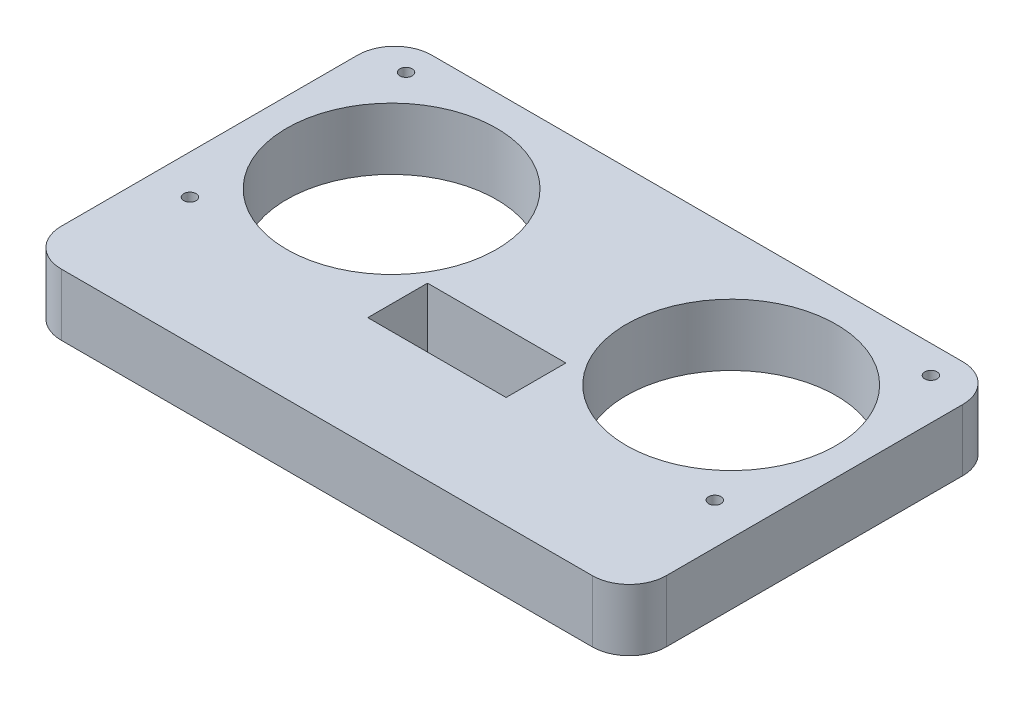
SolidWorks part; units mm, degrees
ref_plane "Front Plane" through (0, 0, 0) normal (0, 0, 1) x (1, 0, 0)
ref_plane "Top Plane" through (0, 0, 0) normal (0, 1, 0) x (1, 0, 0)
ref_plane "Right Plane" through (0, 0, 0) normal (1, 0, 0) x (0, 0, -1)
sketch "Sketch1" plane through (0, 0, 0) normal (0, 1, 0) x (1, 0, 0)
  circle A0 centre (0, 0) radius 20
  circle A1 centre (0, 0) radius 21
  dimension "D1" = 40
  dimension "D2" = 42
extrude "Boss-Extrude1" add sketch "Sketch1" along normal blind 3.5
ref_plane "Plane1" through (0, 3.5, 0) normal (0, 1, 0) x (1, 0, 0)
sketch "Sketch2" plane through (0, 3.5, 0) normal (0, 1, 0) x (1, 0, 0)
  line L0 (-23.55, 0) -> (23.55, 0) construction
  line L1 (-29, -29) -> (29, -29)
  line L2 (-29, -29) -> (-29, 29)
  line L3 (-29, 29) -> (29, 29)
  line L4 (29, -29) -> (29, 29)
  line L5 (-29, -29) -> (29, 29) construction
  line L6 (-29, 29) -> (29, -29) construction
  line L7 (-28.2, -28.2) -> (28.2, -28.2) construction
  line L8 (-28.2, -28.2) -> (-28.2, 28.2) construction
  line L9 (-28.2, 28.2) -> (28.2, 28.2) construction
  line L10 (28.2, -28.2) -> (28.2, 28.2) construction
  line L11 (-28.2, -28.2) -> (28.2, 28.2) construction
  line L12 (-28.2, 28.2) -> (28.2, -28.2) construction
  line L13 (-23.55, 28.2) -> (-23.55, 23.55) construction
  line L14 (-23.55, 23.55) -> (-28.2, 23.55) construction
  line L15 (0, 28.2) -> (0, -28.2) construction
  line L16 (0, 29) -> (0, 49) construction
  line L17 (-22.5, 49) -> (22.5, 49) construction
  line L18 (-22.5, 49) -> (-22.5, 29) construction
  line L19 (22.5, 49) -> (22.5, 29) construction
  line L20 (0, 49) -> (0, 48) construction
  line L21 (-4.9, 48) -> (4.9, 48) construction
  line L22 (-4.9, 48) -> (-4.9, 44.56) construction
  line L23 (-4.9, 44.56) -> (4.9, 44.56) construction
  line L24 (4.9, 44.56) -> (4.9, 48) construction
  line L25 (-24.5, 29) -> (-24.5, 51)
  line L26 (-24.5, 51) -> (24.5, 51)
  line L27 (24.5, 51) -> (24.5, 29)
  line L28 (-13.76, 39) -> (13.76, 39) construction
  line L29 (-5.6, 48.7) -> (5.6, 48.7)
  line L31 (5.6, 43.86) -> (-5.6, 43.86)
  line L32 (-5.6, 43.86) -> (-5.6, 48.7)
  line L33 (5.6, 43.86) -> (5.6, 48.7)
  line L34 (-24.5, 51) -> (-24.5, 59)
  line L35 (-24.5, 59) -> (24.5, 59)
  line L36 (24.5, 59) -> (24.5, 51)
  line L37 (0, 0) -> (34, 0) construction
  line L38 (29, 5) -> (39, 5)
  line L39 (29, -5) -> (39, -5)
  line L40 (39, 5) -> (39, -5)
  line L41 (-29, -5) -> (-39, -5)
  line L42 (-39, 5) -> (-39, -5)
  line L43 (-29, 5) -> (-39, 5)
  circle A0 centre (-23.55, 23.55) radius 2.55 construction
  circle A1 centre (23.55, 23.55) radius 2.55 construction
  circle A2 centre (23.55, -23.55) radius 2.55 construction
  circle A3 centre (-23.55, -23.55) radius 2.55 construction
  circle A4 centre (0, 0) radius 5.5563 construction
  circle A5 centre (13.76, 39) radius 7.5 construction
  circle A6 centre (-13.76, 39) radius 7.5 construction
  circle A7 centre (-13.76, 39) radius 8.5
  circle A8 centre (13.76, 39) radius 8.5
  circle A9 centre (0, 0) radius 6.55
  circle A10 centre (-23.55, 23.55) radius 3.55
  circle A11 centre (23.55, 23.55) radius 3.55
  circle A12 centre (23.55, -23.55) radius 3.55
  circle A13 centre (-23.55, -23.55) radius 3.55
  circle A14 centre (34, 0) radius 2.55
  circle A15 centre (-34, 0) radius 2.55
  point P0 (0, 0)
  point P5 (0, 0)
  point P15 (0, 0)
  point P34 (0, 49)
  point P40 (0, 48)
  point P49 (0, 39)
  point P56 (0, 43.86)
  point P59 (0, 48.7)
  point P70 (34, 0)
  dimension "D4" = 5.1
  dimension "D5" = 11.1125
  dimension "D15" = 15
  dimension "D16" = 17
  dimension "D17" = 0.7
  dimension "D20" = 13.1
  dimension "D21" = 7.1
  dimension "D22" = 8
  dimension "D24" = 5.1
  dimension "D25" = 5
  dimension "D1" = 58
  dimension "D2" = 56.4
  dimension "D3" = 47.1
  dimension "D6" = 20
  dimension "D7" = 45
  dimension "D8" = 1
  dimension "D9" = 9.8
  dimension "D10" = 3.44
  dimension "D11" = 2
  dimension "D12" = 2
  dimension "D13" = 2
  dimension "D14" = 27.52
  dimension "D18" = 0.7
  dimension "D19" = 0.7
  dimension "D23" = 34
  dimension "D26" = 5
extrude "Boss-Extrude2" add sketch "Sketch2" along normal blind 5 contours L1 L4 L3 L2 A4 A1 A0 A2 A3 | L27 L26 L25 L3 A8 A7 L33 L31 L32 L29 | L40 L38 L4 L39 A14 | L2 L43 L42 L41 A15 region at (-28.1798, 3.5, 17) region at (-34, 3.5, 4.8586) region at (29.1414, 3.5, 0) region at (0, 3.5, -40.1992)
sketch "Sketch3" plane through (0, 3.5, 0) normal (0, 1, 0) x (1, 0, 0)
  line L0 (-5.6, 48.7) -> (5.6, 48.7)
  line L1 (5.6, 48.7) -> (5.6, 43.86)
  line L2 (5.6, 43.86) -> (-5.6, 43.86)
  line L3 (-5.6, 43.86) -> (-5.6, 48.7)
  line L4 (-13.76, 47.5) -> (-13.76, 30.5) construction
  line L5 (13.76, 47.5) -> (13.76, 30.5) construction
  line L6 (-24.5, 29) -> (24.5, 29)
  line L7 (24.5, 29) -> (24.5, 51)
  line L8 (24.5, 51) -> (-24.5, 51)
  line L9 (-24.5, 51) -> (-24.5, 29)
  line L10 (-24.5, 51) -> (-24.5, 59)
  line L11 (-24.5, 59) -> (24.5, 59)
  line L12 (24.5, 59) -> (24.5, 51)
  circle A0 centre (-13.76, 39) radius 8.5 construction
  circle A1 centre (-13.76, 39) radius 8.5
  circle A2 centre (13.76, 39) radius 8.5 construction
  circle A3 centre (13.76, 39) radius 8.5
  dimension "D1" = 8
sketch "Sketch4" plane through (0, 3.5, 0) normal (0, 1, 0) x (1, 0, 0)
  line L4 (-5.6791, 42.84) -> (-5.6791, 38)
  line L5 (5.5209, 38) -> (5.5209, 42.84)
  line L10 (-24.5, 29) -> (-24.5, 37)
  line L11 (-24.5, 51) -> (-24.5, 29) construction
  line L12 (24.5, 29) -> (24.5, 37)
  line L13 (24.5, 29) -> (24.5, 51) construction
  line L14 (-24.5, 37) -> (-24.5, 59)
  line L15 (24.5, 37) -> (24.5, 59)
  line L16 (-24.5, 59) -> (24.5, 59)
  line L17 (-24.5, 37) -> (24.5, 37)
  line L18 (0, 59) -> (0, 37) construction
  line L23 (-5.6791, 38) -> (5.5209, 38)
  line L24 (5.5209, 42.84) -> (-5.6791, 42.84)
  line L25 (-5.6791, 58) -> (5.5209, 58) construction
  line L26 (5.5209, 58) -> (5.5209, 53.16) construction
  line L27 (5.5209, 53.16) -> (-5.6791, 53.16) construction
  line L28 (-5.6791, 53.16) -> (-5.6791, 58) construction
  line L29 (-13.75, 56.5) -> (-13.75, 39.5) construction
  line L30 (-13.75, 48) -> (13.75, 48) construction
  circle A4 centre (-13.75, 48) radius 8.5
  circle A5 centre (13.75, 48) radius 8.5
  point P53 (0, 48)
  dimension "D2" = 17
  dimension "D1" = 8
  dimension "D3" = 22
  dimension "D4" = 1
  dimension "D5" = 5.5209
  dimension "D6" = 11.2
  dimension "D7" = 4.84
  dimension "D8" = 27.5
extrude "Ignore" add sketch "Sketch3" along normal blind 5 contours L3 L2 L1 L0 | L12 L11 L10 L8 | A3 | A1 region at (0, 3.5, -46.28) region at (0, 3.5, -55) region at (-13.76, 3.5, -39) region at (13.76, 3.5, -39)
extrude "Cut-Extrude2" cut sketch "Sketch4" along normal through all contours A4 | A5 | L28 L27 L26 L25 | L5 L24 L4 L23 region at (-0.0791, 3.5, -40.42) region at (-13.75, 3.5, -48) region at (13.75, 3.5, -48)
fillet "Fillet1" radius 3 10 edges at (29, 6, -29) (39, 6, 5) (39, 6, -5) (29, 6, 29) (-29, 6, 29) (-39, 6, 5) (-39, 6, -5) (-29, 6, -29) (24.5, 6, -59) (-24.5, 6, -59)
sketch "Sketch5" plane through (0, 0, 0) normal (0, 0, 1) x (1, 0, 0)
  line L0 (-21, 3.5) -> (21, 3.5)
  line L1 (21, 3.5) -> (21, 0)
  line L2 (21, 0) -> (-21, 0)
  line L3 (-21, 0) -> (-21, 3.5)
extrude "Cut-Extrude3" cut sketch "Sketch5" against normal mid plane 50
sketch "Sketch6" plane through (0, 8.5, 0) normal (0, 1, 0) x (1, 0, 0)
  line L0 (-26, 29) -> (24.5, 29)
  line L1 (24.5, 29) -> (43.3219, 29)
  line L2 (43.3219, 29) -> (43.3219, -33.143)
  line L5 (-38.2971, 29) -> (-26, 29)
  line L6 (43.3219, -33.143) -> (-52.0728, -33.143)
  line L7 (-52.0728, -33.143) -> (-52.0728, 29)
  line L8 (-52.0728, 29) -> (-38.2971, 29)
extrude "Cut-Extrude5" cut sketch "Sketch6" against normal blind 10
fillet "Fillet2" radius 3 2 edges at (24.5, 6, -29) (-24.5, 6, -29)
sketch "Sketch8" plane through (0, 3.5, 0) normal (0, -1, 0) x (1, 0, 0)
  line L0 (-22.25, -48) -> (22.25, -48) construction
  line L1 (-0.0791, -42.84) -> (-0.0791, -54.7233) construction
  line L2 (5.5209, -42.84) -> (-5.6791, -42.84) construction
  circle A0 centre (-13.75, -48) radius 8.5 construction
  circle A1 centre (13.75, -48) radius 8.5 construction
  circle A2 centre (21.1709, -39.25) radius 0.5
  circle A3 centre (21.1709, -56.75) radius 0.5
  circle A4 centre (-21.3291, -56.75) radius 0.5
  circle A5 centre (-21.3291, -39.25) radius 0.5
  dimension "D2" = 1
  dimension "D3" = 8.75
  dimension "D1" = 44.5
  dimension "D4" = 8.75
  dimension "D5" = 42.5
  dimension "D6" = 42.5
extrude "Cut-Extrude6" cut sketch "Sketch8" against normal blind 20
